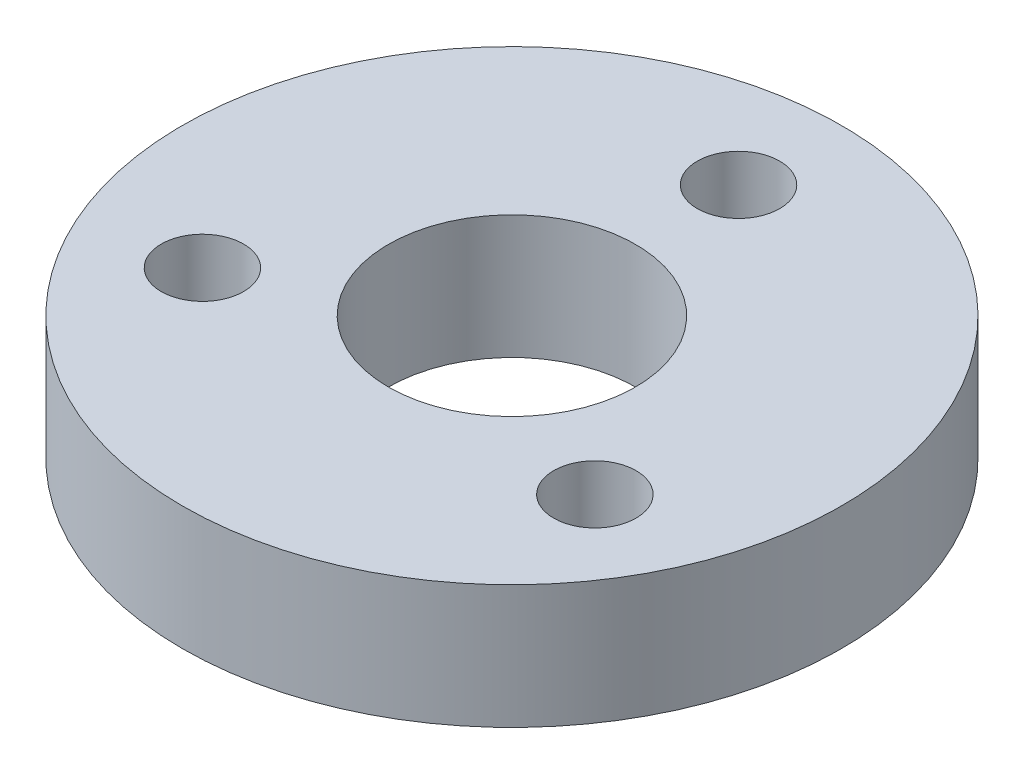
SolidWorks part; units mm, degrees
ref_plane "Front Plane" through (0, 0, 0) normal (0, 0, 1) x (1, 0, 0)
ref_plane "Top Plane" through (0, 0, 0) normal (0, 1, 0) x (1, 0, 0)
ref_plane "Right Plane" through (0, 0, 0) normal (1, 0, 0) x (0, 0, -1)
sketch "Sketch1" plane through (0, 0, 0) normal (0, 1, 0) x (1, 0, 0)
  line L0 (0, 8) -> (0, -8) construction
  circle A0 centre (0, 0) radius 3
  circle A1 centre (0, 0) radius 8
  circle A2 centre (0, 0) radius 5.5 construction
  circle A3 centre (0, 5.5) radius 1
  circle A4 centre (4.7631, -2.75) radius 1
  circle A5 centre (-4.7631, -2.75) radius 1
  point P15 (0, 0)
  point P18 (0, 0)
  dimension "D1" = 6
  dimension "D2" = 16
  dimension "D3" = 2.5
  dimension "D4" = 2
  dimension "D5" = 3
extrude "Boss-Extrude1" add sketch "Sketch1" along normal blind 3
